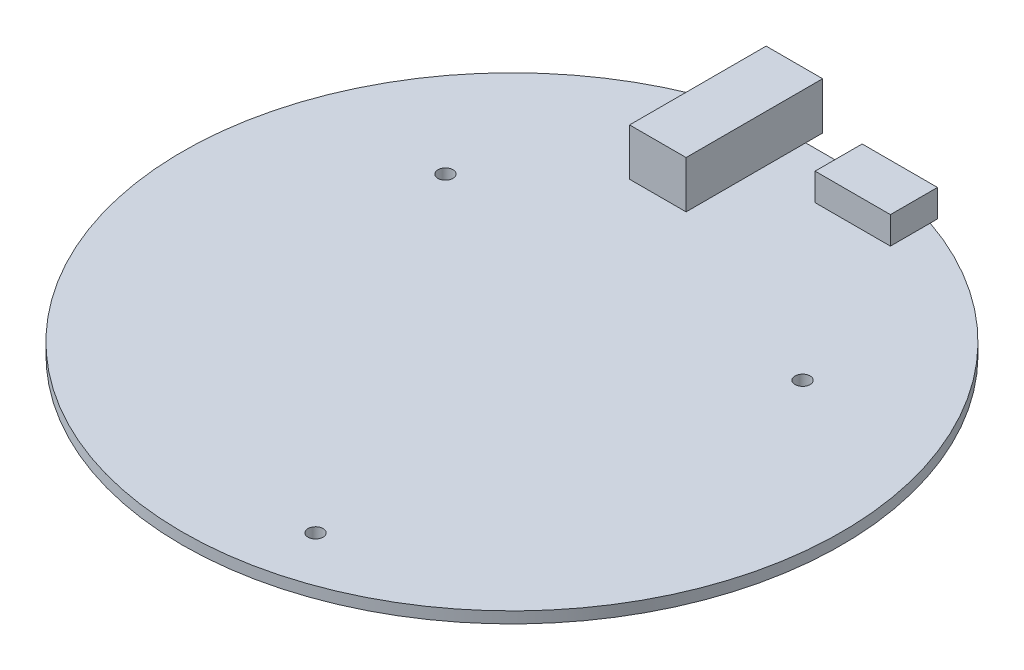
SolidWorks part; units mm, degrees
ref_plane "Front Plane" through (0, 0, 0) normal (0, 0, 1) x (1, 0, 0)
ref_plane "Top Plane" through (0, 0, 0) normal (0, 1, 0) x (1, 0, 0)
ref_plane "Right Plane" through (0, 0, 0) normal (1, 0, 0) x (0, 0, -1)
sketch "Sketch1" plane through (0, 0, 0) normal (0, 1, 0) x (1, 0, 0)
  line L0 (0, -35) -> (0, 33.9) construction
  line L1 (-8.7057, 33.9) -> (8.7057, 33.9)
  line L2 (0, 33.9) -> (0, 11.9) construction
  line L3 (0, 0) -> (18.9638, 11.9) construction
  line L4 (0, 11.9) -> (18.9638, 11.9) construction
  line L5 (0, -35) -> (0, -28) construction
  line L6 (0, -28) -> (7.14, -28) construction
  line L8 (-8.7057, 33.9) -> (-8.7057, 35.7) construction
  line L9 (-8.7057, 35.7) -> (-2.7057, 35.7) construction
  line L10 (-8.7057, 33.9) -> (-8.7057, 35.7)
  line L11 (-8.7057, 35.7) -> (-2.7057, 35.7)
  line L12 (-2.7057, 35.7) -> (-2.7057, 33.9)
  line L13 (-8.7057, 33.9) -> (-8.7057, 21.2)
  line L14 (-2.7057, 33.9) -> (-2.7057, 21.2)
  line L15 (-8.7057, 21.2) -> (-2.7057, 21.2)
  line L18 (-2.7057, 33.9) -> (3.8943, 33.9)
  arc A1 (-8.7057, 33.9) -> (8.7057, 33.9) centre (0, 0) ccw
  circle A2 centre (18.9638, 11.9) radius 0.8
  circle A3 centre (-18.9638, 11.9) radius 0.8
  circle A4 centre (7.14, -28) radius 0.8
  point P14 (0, 0)
  point P19 (0, 0)
  point P21 (0, 0)
  dimension "D1" = 35
  dimension "D6" = 1.6
  dimension "D10" = 1.6
  dimension "D2" = 68.9
  dimension "D3" = 17.4115
  dimension "D4" = 22
  dimension "D5" = 22.3883
  dimension "D7" = 7
  dimension "D8" = 7.14
  dimension "D11" = 1.8
  dimension "D12" = 6
  dimension "D13" = 12.7
  dimension "D16" = 6.6
extrude "Boss-Extrude1" add sketch "Sketch1" along normal blind 5 contours L13 L15 L14 L12 L11 L10
extrude "Boss-Extrude3" add sketch "Sketch1<4>" against normal blind 1.2 contours L13 A1 L1 L14 L15 A4 A2 A3 | L13 L15 L14 L1 region at (-5.7057, 0, -27.55) region at (0.112, 0, 0.6743)
sketch "Sketch1<4>" plane through (0, 0, 0) normal (0, 1, 0) x (1, 0, 0) same geometry as "Sketch1"
sketch "Sketch4" plane through (0, 0, 0) normal (0, 1, 0) x (1, 0, 0)
  line L0 (-2.7057, 33.9) -> (3.2943, 33.9)
  line L1 (-8.7057, 33.9) -> (8.7057, 33.9) construction
  line L2 (3.2943, 33.9) -> (3.2943, 28.9)
  line L3 (3.2943, 28.9) -> (11.2943, 28.9)
  line L4 (3.2943, 33.9) -> (11.2943, 33.9)
  line L5 (11.2943, 33.9) -> (11.2943, 28.9)
  line L6 (0, 33.9) -> (0, 0) construction
  line L7 (3.2943, 33.9) -> (11.2943, 33.9)
  dimension "D1" = 8
  dimension "D2" = 5
  dimension "D3" = 6
extrude "Boss-Extrude5" add sketch "Sketch4" along normal blind 2.9 contours L5 L4 L2 L3 region at (7.2943, 0, -31.4)
